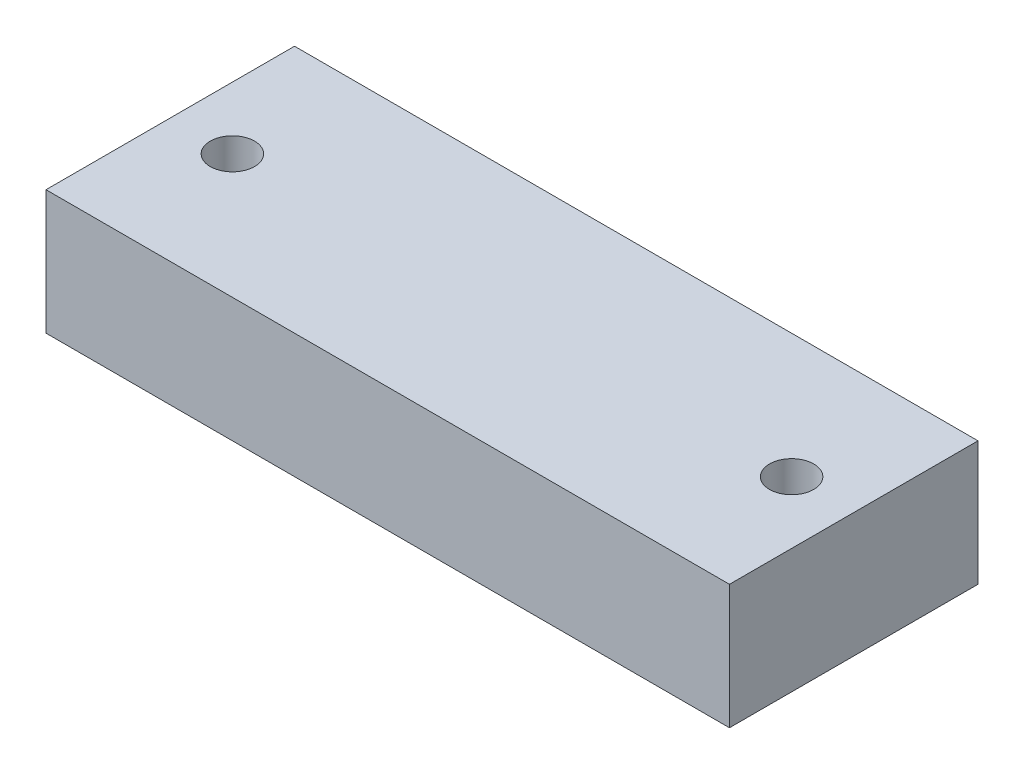
SolidWorks part; units mm, degrees
ref_plane "Front Plane" through (0, 0, 0) normal (0, 0, 1) x (1, 0, 0)
ref_plane "Top Plane" through (0, 0, 0) normal (0, 1, 0) x (1, 0, 0)
ref_plane "Right Plane" through (0, 0, 0) normal (1, 0, 0) x (0, 0, -1)
sketch "Sketch1" plane through (0, 0, 0) normal (0, 1, 0) x (1, 0, 0)
  line L1 (-17.4625, 6.35) -> (17.4625, 6.35)
  line L2 (-17.4625, 6.35) -> (-17.4625, -6.35)
  line L3 (-17.4625, -6.35) -> (17.4625, -6.35)
  line L4 (17.4625, 6.35) -> (17.4625, -6.35)
  line L5 (-17.4625, 6.35) -> (17.4625, -6.35) construction
  line L6 (-17.4625, -6.35) -> (17.4625, 6.35) construction
  point P0 (0, 0)
  dimension "D1" = 34.925
  dimension "D2" = 12.7
extrude "Boss-Extrude1" add sketch "Sketch1" along normal blind 6.35
hole_wizard "#4-40 Tapped Hole1" positions "Sketch2" profile "Sketch3" tap size "#4-40" standard "ANSI Inch" end condition through all
sketch "Sketch2" plane through (0, 6.35, 0) normal (0, 1, 0) x (1, 0, 0)
  point P0 (-14.2875, 0)
  point P3 (14.2875, 0)
sketch "Sketch3" plane through (-14.2875, 6.35, 0) normal (1, 0, 0) x (0, 0, 1)
  line L0 (0, 0) -> (0, 6.35)
  line L1 (0, 6.35) -> (1.1303, 6.35)
  line L2 (1.1303, 6.35) -> (1.1303, 0)
  line L5 (1.1303, 0) -> (0, 0)
  line L11 (0, -6.35) -> (0, 107.95) construction
  dimension "Thru Tap Drill Dia." = 2.2606
  dimension "Thru Tap Drill Depth" = 6.35
cosmetic thread "Hole Thread1" parameters "D2"=2.8448
cosmetic thread "Hole Thread2" parameters "D2"=2.8448
